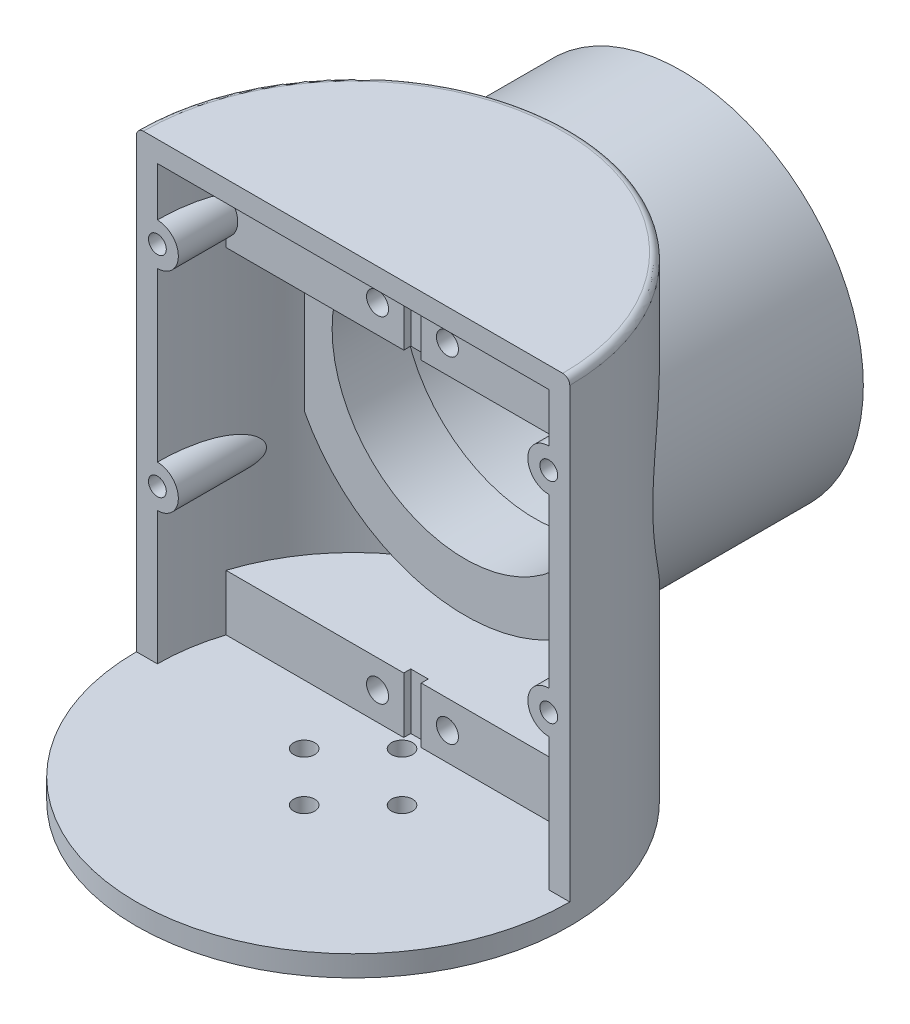
SolidWorks part; units mm, degrees
material "ABS"
ref_plane "Спереди" through (0, 0, 0) normal (0, 0, 1) x (1, 0, 0)
ref_plane "Сверху" through (0, 0, 0) normal (0, 1, 0) x (1, 0, 0)
ref_plane "Справа" through (0, 0, 0) normal (1, 0, 0) x (0, 0, -1)
sketch "Эскиз3" plane through (0, 0, 0) normal (1, 0, 0) x (0, 0, -1)
  line L0 (0, 68.2882) -> (0, 0) construction
  line L1 (0, 0) -> (31, 0)
  line L2 (31, 0) -> (31, 68)
  line L3 (31, 68) -> (0, 68)
  line L4 (0, 68) -> (0, 65)
  line L5 (0, 65) -> (28, 65)
  line L6 (28, 65) -> (28, 3)
  line L7 (28, 3) -> (0, 3)
  line L8 (0, 3) -> (0, 0)
  dimension "D1" = 62
  dimension "D2" = 68
  dimension "D3" = 3
  dimension "D4" = 3
  dimension "D5" = 3
revolve "Повернуть2" add sketch "Эскиз3" angle 360 about L0
sketch "Эскиз4" plane through (0, 68, 0) normal (0, 1, 0) x (1, 0, 0)
  line L0 (-31, 0) -> (31, 0)
  circle A0 centre (0, 0) radius 31 construction
  arc A1 (31, 0) -> (-31, 0) centre (0, 0) cw
extrude "Вырез-Вытянуть1" cut sketch "Эскиз4" against normal blind 65
sketch "Эскиз6" plane through (0, 0, 0) normal (0, -1, 0) x (1, 0, 0)
  circle A0 centre (7, 0) radius 1.5
  dimension "D1" = 3
  dimension "D2" = 7
extrude "Вырез-Вытянуть3" cut sketch "Эскиз6" against normal up to surface (3 mm away) up to face at (0, 3, 0.75)
pattern_circular "Круговой массив1" count 4 over 360 about axis through (0, 68.2882, 0) along (0, 1, 0) of "Вырез-Вытянуть3"
sketch "Эскиз7" plane through (0, 0, 0) normal (0, 0, 1) x (1, 0, 0)
  circle A0 centre (0, 41) radius 21
  circle A1 centre (0, 41) radius 26
  dimension "D1" = 52
  dimension "D2" = 42
  dimension "D3" = 41
extrude "Бобышка-Вытянуть1" add sketch "Эскиз7" against normal blind 31 from offset 16 offset against normal yes
sketch "Эскиз22" plane through (0, 0, -16) normal (0, 0, 1) x (1, 0, 0)
  line L0 (28, 3) -> (-28, 3) construction
  line L1 (-22.9783, 65) -> (22.9783, 65)
  line L2 (-22.9783, 65) -> (-22.9783, 51)
  line L3 (-22.9783, 51) -> (22.9783, 51)
  line L4 (22.9783, 65) -> (22.9783, 51)
  line L5 (-22.9783, 3) -> (22.9783, 3)
  line L6 (-28, 65) -> (-10, 65) construction
  line L7 (-22.9783, 28.8345) -> (-22.9783, 53.1655) construction
  line L8 (22.9783, 53.1655) -> (22.9783, 28.8345) construction
  line L9 (-22.9783, 3) -> (-22.9783, 11)
  line L10 (-22.9783, 11) -> (22.9783, 11)
  line L11 (22.9783, 3) -> (22.9783, 11)
  dimension "D1" = 14
  dimension "D2" = 8
extrude "Бобышка-Вытянуть7" add sketch "Эскиз22" against normal up to surface (7.5 mm away) from offset 7.5 up to face at (0.4346, 42.0206, -16.4737)
sketch "Эскиз8" plane through (0, 0, -47) normal (0, 0, -1) x (-1, 0, 0)
  circle A0 centre (0, 41) radius 21
  dimension "D1" = 42
  dimension "D2" = 41
extrude "Вырез-Вытянуть4" cut sketch "Эскиз8" against normal up to surface (31 mm away) up to face at (0, 36.1391, -16)
sketch "Эскиз11" plane through (0, 0, 0) normal (0, 0, 1) x (1, 0, 0)
  line L0 (-28, 65) -> (-28, 3) construction
  line L1 (28, 3) -> (28, 65) construction
  line L3 (-28, 25) -> (28, 25) construction
  line L4 (-28, 25) -> (-28, 55) construction
  line L5 (-28, 55) -> (28, 55) construction
  line L6 (28, 25) -> (28, 55) construction
  circle A0 centre (-28, 55) radius 3
  circle A1 centre (-28, 25) radius 3
  circle A2 centre (28, 25) radius 3
  circle A3 centre (28, 55) radius 3
  point P12 (0, 25)
  point P15 (28, 40)
  dimension "D1" = 6
  dimension "D2" = 6
  dimension "D3" = 6
  dimension "D4" = 6
  dimension "D5" = 30
  dimension "D6" = 40
extrude "Бобышка-Вытянуть3" add sketch "Эскиз11" against normal up to surface (12.6095 mm away) up to face at (0.2009, 31.4276, -13.2427)
hole_wizard "Сверло под метчик  спиральное M2.52" positions "Эскиз15" profile "Эскиз16" hole size "M2.5x0.45" standard "Ansi Metric"
sketch "Эскиз15" plane through (0, 0, 0) normal (0, 0, 1) x (1, 0, 0)
  point P0 (-28, 55)
  point P3 (28, 55)
  point P6 (28, 25)
  point P9 (-28, 25)
sketch "Эскиз16" plane through (-28, 55, 0) normal (1, 0, 0) x (0, -1, 0)
  line L0 (0, 0) -> (0, 5.7661)
  line L1 (0, 5.7661) -> (1.275, 5)
  line L2 (1.275, 5) -> (1.275, 0)
  line L5 (1.275, 0) -> (0, 0)
  line L10 (0, 5.7661) -> (-1.275, 5) construction
  line L11 (0, -6.35) -> (0, 107.95) construction
  dimension "Диаметр отверстия" = 2.55
  dimension "Глубина отверстия" = 5
  dimension "Угол заточки сверла" = 118
hole_wizard "Отверстие обработанное метчиком M2x0.41" positions "Эскиз18" profile "Эскиз19" tap size "M2x0.4" standard "HASCO Metric"
sketch "Эскиз18" plane through (0, 0, -47) normal (0, 0, -1) x (-1, 0, 0)
  line L2 (0, 41) -> (23, 41) construction
  line L4 (0, 41) -> (16.2635, 57.2635) construction
  circle A1 centre (0, 41) radius 23 construction
  point P0 (16.2635, 57.2635)
  dimension "D1" = 46
  dimension "D2" = 45
sketch "Эскиз19" plane through (-16.2635, 57.2635, -47) normal (1, 0, 0) x (0, 1, 0)
  line L0 (0, 0) -> (0, 10.4807)
  line L1 (0, 10.4807) -> (0.8, 10)
  line L2 (0.8, 10) -> (0.8, 0.225)
  line L3 (0.8, 0.225) -> (1.025, 0)
  line L5 (1.025, 0) -> (0, 0)
  line L6 (-0.8, 0.225) -> (-1.025, 0) construction
  line L10 (0, 10.4807) -> (-0.8, 10) construction
  line L11 (0, -6.35) -> (0, 107.95) construction
  dimension "Диаметр сверла" = 1.6
  dimension "Глубина сверла" = 10
  dimension "Диаметр передней зенковки" = 2.05
  dimension "Угол передней зенковки" = 90
  dimension "Угол заточки сверла" = 118
cosmetic thread "Отверстие резьбы1" parameters "D1"=8, "D2"=2
pattern_circular "Круговой массив2" count 8 over 360 about axis through (0, 41, -47) along (0, 0, 1) of "Отверстие обработанное метчиком M2x0.41"
ref_plane "Плоскость1" through (0, 0, -26) normal (0, 0, -1) x (-1, 0, 0)
sketch "Эскиз20" plane through (0, 0, -26) normal (0, 0, -1) x (-1, 0, 0)
  circle A0 centre (0, 41) radius 19
  circle A1 centre (0, 41) radius 26
  dimension "D1" = 38
  dimension "D2" = 52
extrude "Бобышка-Вытянуть6" add sketch "Эскиз20" against normal blind 10 contours A1 A0 region at (25.2646, 41, -26)
fillet "Скругление1" radius 1 1 edges at (0, 68, -31)
sketch "Эскиз23" plane through (-22.9783, 0, 0) normal (-1, 0, 0) x (0, 0, 1)
  line L1 (-16, 65) -> (-8.5, 65)
  line L2 (-16, 65) -> (-16, 51)
  line L3 (-16, 51) -> (-8.5, 51)
  line L4 (-8.5, 65) -> (-8.5, 51)
  line L5 (-16, 11) -> (-8.5, 11)
  line L6 (-16, 11) -> (-16, 3)
  line L7 (-16, 3) -> (-8.5, 3)
  line L8 (-8.5, 11) -> (-8.5, 3)
extrude "Бобышка-Вытянуть8" add sketch "Эскиз23" along normal up to next
mirror "Зеркальное отражение1" about plane through (0, 0, 0) normal (1, 0, 0) of "Бобышка-Вытянуть8"
sketch "Эскиз24" plane through (0, 0, -8.5) normal (0, 0, 1) x (1, 0, 0)
  line L0 (0, 51) -> (0, 66.3483) construction
  line L1 (-26.6786, 51) -> (26.6786, 51) construction
  line L2 (1.25, 51) -> (-1.25, 51)
  line L3 (-1.25, 51) -> (-1.25, 65)
  line L4 (-1.25, 65) -> (1.25, 65)
  line L5 (28, 65) -> (-28, 65) construction
  line L6 (1.25, 51) -> (1.25, 65)
  line L7 (1.25, 3) -> (-1.25, 3)
  line L8 (-26.6786, 3) -> (0, 3) construction
  line L9 (-1.25, 3) -> (-1.25, 11)
  line L10 (26.6786, 11) -> (-26.6786, 11) construction
  line L11 (-1.25, 11) -> (1.25, 11)
  line L12 (1.25, 3) -> (1.25, 11)
  point P14 (0, 65)
  point P23 (0, 11)
  point P24 (0, 3)
  dimension "D1" = 2.5
extrude "Вырез-Вытянуть5" cut sketch "Эскиз24" against normal blind 1
hole_wizard "Сверло под метчик  спиральное M31" positions "Эскиз25" profile "Эскиз26" hole size "M3x0.5" standard "Ansi Metric"
sketch "Эскиз25" plane through (0, 0, -8.5) normal (0, 0, 1) x (1, 0, 0)
  line L0 (-26.6786, 51) -> (-1.25, 51) construction
  line L1 (-1.25, 51) -> (1.25, 51) construction
  line L3 (-1.25, 11) -> (-26.6786, 11) construction
  line L4 (1.25, 11) -> (-1.25, 11) construction
  point P0 (-5, 55)
  point P2 (5, 55)
  point P9 (0, 51)
  point P13 (-5, 7)
  point P15 (5, 7)
  point P25 (0, 11)
  dimension "D1" = 10
  dimension "D2" = 4
  dimension "D3" = 5
  dimension "D4" = 10
  dimension "D5" = 4
  dimension "D6" = 5
sketch "Эскиз26" plane through (-5, 55, -8.5) normal (1, 0, 0) x (0, -1, 0)
  line L0 (0, 0) -> (0, 10.9464)
  line L1 (0, 10.9464) -> (1.575, 10)
  line L2 (1.575, 10) -> (1.575, 0)
  line L5 (1.575, 0) -> (0, 0)
  line L10 (0, 10.9464) -> (-1.575, 10) construction
  line L11 (0, -6.35) -> (0, 107.95) construction
  dimension "Диаметр отверстия" = 3.15
  dimension "Глубина отверстия" = 10
  dimension "Угол заточки сверла" = 118
